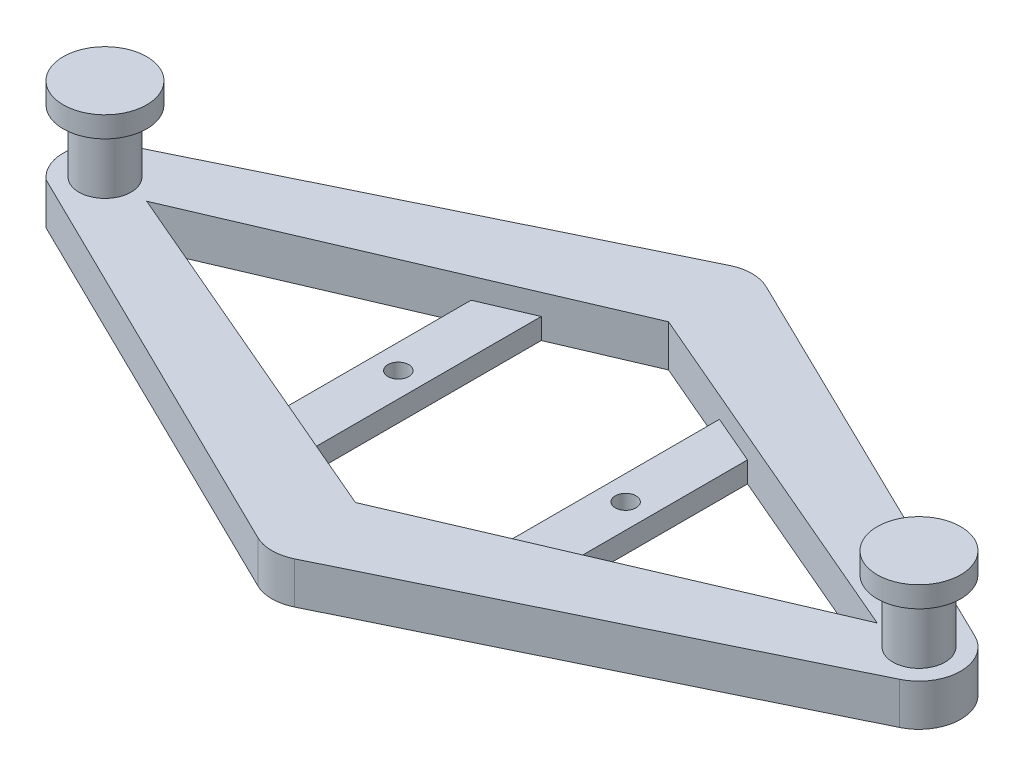
SolidWorks part; units mm, degrees
ref_plane "Front Plane" through (0, 0, 0) normal (0, 0, 1) x (1, 0, 0)
ref_plane "Top Plane" through (0, 0, 0) normal (0, 1, 0) x (1, 0, 0)
ref_plane "Right Plane" through (0, 0, 0) normal (1, 0, 0) x (0, 0, -1)
sketch "Base" plane through (0, 0, 0) normal (0, 1, 0) x (1, 0, 0)
  line L0 (0, 0) -> (49.53, 0)
  line L1 (0, 0) -> (-49.53, 0)
  line L2 (0, 0) -> (0, 24.13)
  line L3 (0, 0) -> (0, -24.13)
  line L4 (-44.45, 0) -> (0, 19.05)
  line L5 (0, 19.05) -> (44.45, 0)
  line L6 (44.45, 0) -> (0, -19.05)
  line L7 (0, -19.05) -> (-44.45, 0)
  line L8 (-51.7549, 4.5669) -> (-2.2249, 28.6969)
  line L9 (-52.8265, -3.8652) -> (-2.238, -28.6905)
  line L10 (2.2249, -28.6969) -> (51.7549, -4.5669)
  line L11 (51.7077, 4.5895) -> (2.2249, 28.6969)
  arc A0 (-51.7549, 4.5669) -> (-52.8265, -3.8652) centre (-49.53, 0) ccw
  arc A1 (2.2249, 28.6969) -> (-2.2249, 28.6969) centre (0, 24.13) ccw
  arc A2 (51.7549, -4.5669) -> (51.7077, 4.5895) centre (49.53, 0) ccw
  arc A3 (-2.238, -28.6905) -> (2.2249, -28.6969) centre (0, -24.13) ccw
  point P10 (0, 19.05)
  point P11 (-44.45, 0)
  point P12 (0, -19.05)
  point P13 (44.45, 0)
  point P27 (-51.7549, 4.5669)
  point P28 (-52.8265, -3.8652)
  point P29 (-2.238, -28.6905)
  point P30 (2.2249, -28.6969)
  point P31 (51.7549, -4.5669)
  point P32 (51.8018, 4.5437)
  point P33 (2.2249, 28.6969)
  point P34 (-2.2249, 28.6969)
sketch "Sketch4" plane through (0, 0, 0) normal (0, 1, 0) x (1, 0, 0)
  line L0 (-44.45, 0) -> (0, 19.05)
  line L1 (0, 19.05) -> (44.45, 0)
  line L2 (44.45, 0) -> (0, -19.05)
  line L3 (0, -19.05) -> (-44.45, 0)
  line L4 (-51.7549, 4.5669) -> (-2.2249, 28.6969)
  line L5 (-52.8265, -3.8652) -> (-2.238, -28.6905)
  line L6 (2.2249, -28.6969) -> (51.7549, -4.5669)
  line L7 (51.7077, 4.5895) -> (2.2249, 28.6969)
  arc A0 (-51.7549, 4.5669) -> (-52.8265, -3.8652) centre (-49.53, 0) ccw
  arc A1 (2.2249, 28.6969) -> (-2.2249, 28.6969) centre (0, 24.13) ccw
  arc A2 (51.7549, -4.5669) -> (51.7077, 4.5895) centre (49.53, 0) ccw
  arc A3 (-2.238, -28.6905) -> (2.2249, -28.6969) centre (0, -24.13) ccw
extrude "Boss-Extrude1" add sketch "Sketch4" along normal blind 5.08
sketch "Sketch5" plane through (0, 5.08, 0) normal (0, 1, 0) x (1, 0, 0)
  circle A0 centre (-49.53, 0) radius 3.175
  circle A1 centre (49.53, 0) radius 3.175
extrude "Boss-Extrude2" add sketch "Sketch5" along normal blind 7.62
sketch "Sketch8" plane through (0, 0, 0) normal (0, 1, 0) x (1, 0, 0)
  line L0 (-12.6059, 13.6475) -> (-12.6059, -13.6475)
  line L1 (-44.45, 0) -> (0, 19.05) construction
  line L2 (0, -19.05) -> (-44.45, 0) construction
  line L3 (-16.8237, 11.8398) -> (-16.8237, -11.8398)
  line L4 (0, 19.05) -> (0, -19.05)
  line L5 (12.6059, 13.6475) -> (12.6059, -13.6475)
  line L6 (16.8237, 11.8398) -> (16.8237, -11.8398)
  line L7 (-16.8237, 0) -> (-12.6059, 0)
  line L8 (12.6059, 0) -> (16.8237, 0)
  line L9 (-16.8237, 11.8398) -> (-12.6059, 13.6475)
  line L10 (-16.8237, -11.8398) -> (-12.6059, -13.6475)
  line L11 (12.6059, 13.6475) -> (16.8237, 11.8398)
  line L12 (12.6059, -13.6475) -> (16.8237, -11.8398)
  circle A0 centre (14.7148, 0) radius 1.27
  circle A1 centre (-14.7148, 0) radius 1.27
sketch "Sketch9" plane through (0, 0, 0) normal (0, 1, 0) x (1, 0, 0)
  line L0 (-10.839, 14.4047) -> (-10.839, -14.4047)
  line L1 (-16.8237, 11.8398) -> (-16.8237, -11.8398)
  line L4 (-16.8237, 11.8398) -> (-10.839, 14.4047)
  line L5 (-16.8237, -11.8398) -> (-10.839, -14.4047)
  line L8 (-44.45, 0) -> (0, 19.05) construction
  line L9 (0, -19.05) -> (-44.45, 0) construction
  line L10 (-16.8237, 0) -> (-10.839, 0)
  line L11 (0, 19.05) -> (0, -19.05)
  line L12 (16.8237, 11.8398) -> (10.839, 14.4047)
  line L13 (16.8237, -11.8398) -> (10.839, -14.4047)
  line L14 (16.8237, 11.8398) -> (16.8237, -11.8398)
  line L15 (10.839, 14.4047) -> (10.839, -14.4047)
  circle A2 centre (-13.8314, 0) radius 1.27
  circle A3 centre (13.8314, 0) radius 1.27
  point P8 (-13.8314, 13.1223)
  point P25 (13.8314, 13.1223)
sketch "Sketch11" plane through (0, 12.7, 0) normal (0, 1, 0) x (1, 0, 0)
  circle A0 centre (49.53, 0) radius 5.08
sketch "Sketch12" plane through (0, 12.7, 0) normal (0, 1, 0) x (1, 0, 0)
  circle A0 centre (49.53, 0) radius 5.08
extrude "Boss-Extrude4" add sketch "Sketch12" along normal blind 2.54
sketch "Sketch13" plane through (0, 12.7, 0) normal (0, 1, 0) x (1, 0, 0)
  circle A0 centre (-49.53, 0) radius 5.08
sketch "Sketch14" plane through (0, 12.7, 0) normal (0, 1, 0) x (1, 0, 0)
  circle A0 centre (-49.53, 0) radius 5.08
extrude "Boss-Extrude5" add sketch "Sketch14" along normal blind 2.54
sketch "Sketch15" plane through (0, 0, 0) normal (0, 1, 0) x (1, 0, 0)
  line L0 (-10.839, 14.4047) -> (-10.839, -14.4047)
  line L1 (-16.8237, 11.8398) -> (-16.8237, -11.8398)
  line L2 (-16.8237, 11.8398) -> (-10.839, 14.4047)
  line L3 (-16.8237, -11.8398) -> (-10.839, -14.4047)
  line L4 (16.8237, 11.8398) -> (10.839, 14.4047)
  line L5 (16.8237, -11.8398) -> (10.839, -14.4047)
  line L6 (16.8237, 11.8398) -> (16.8237, -11.8398)
  line L7 (10.839, 14.4047) -> (10.839, -14.4047)
  circle A0 centre (-13.8314, 0) radius 1.27
  circle A1 centre (13.8314, 0) radius 1.27
  point P4 (-10.839, 0)
  point P7 (-13.8314, 13.1223)
extrude "Boss-Extrude6" add sketch "Sketch15" along normal blind 2.54 separate body
